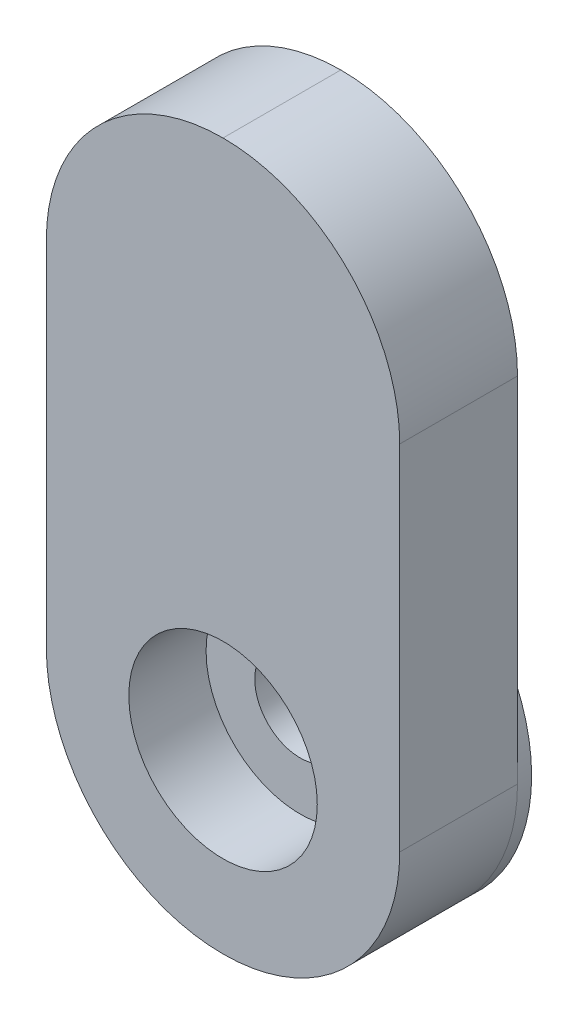
SolidWorks part; units mm, degrees
ref_plane "Front Plane" through (0, 0, 0) normal (0, 0, 1) x (1, 0, 0)
ref_plane "Top Plane" through (0, 0, 0) normal (0, 1, 0) x (1, 0, 0)
ref_plane "Right Plane" through (0, 0, 0) normal (1, 0, 0) x (0, 0, -1)
sketch "Sketch1" plane through (0, 0, 0) normal (0, 0, 1) x (1, 0, 0)
  line L1 (-9.525, 38.1) -> (9.525, 38.1)
  line L2 (-9.525, 38.1) -> (-9.525, 0)
  line L3 (-9.525, 0) -> (9.525, 0)
  line L4 (9.525, 38.1) -> (9.525, 0)
  line L5 (-9.525, 38.1) -> (9.525, 0) construction
  line L6 (-9.525, 0) -> (9.525, 38.1) construction
  point P0 (0, 19.05)
  dimension "D1" = 19.05
  dimension "D2" = 38.1
extrude "Boss-Extrude1" add sketch "Sketch1" along normal blind 6.35
hole_wizard "CBORE for #8 Socket Head Cap Screw1" positions "Sketch2" profile "Sketch3" counterbore size "#8" standard "ANSI Inch" end condition through all
sketch "Sketch2" plane through (0, 0, 6.35) normal (0, 0, 1) x (1, 0, 0)
  line L0 (-9.525, 0) -> (9.525, 0) construction
  point P0 (0, 9.525)
  dimension "D1" = 9.525
sketch "Sketch3" plane through (0, 9.525, 6.35) normal (1, 0, 0) x (0, -1, 0)
  line L0 (0, 0) -> (0, 6.35)
  line L1 (0, 6.35) -> (2.4575, 6.35)
  line L3 (2.4575, 6.35) -> (2.4575, 4.1656)
  line L4 (2.4575, 4.1656) -> (5.08, 4.1656)
  line L5 (5.08, 4.1656) -> (5.08, 0)
  line L7 (5.08, 0) -> (0, 0)
  line L11 (0, -6.35) -> (0, 107.95) construction
  dimension "Thru Hole Dia." = 4.9149
  dimension "Thru Hole Depth" = 6.35
  dimension "C'Bore Dia." = 10.16
  dimension "C'Bore Depth" = 4.1656
sketch "Sketch4" plane through (0, 0, 0) normal (0, 0, -1) x (-1, 0, 0)
  circle A0 centre (0, 9.525) radius 2.4575
  circle A1 centre (0, 9.525) radius 9.525
  circle A2 centre (0, 9.525) radius 2.4575 construction
  dimension "D1" = 19.05
extrude "Boss-Extrude2" add sketch "Sketch4" along normal blind 0.762
sketch "Sketch5" plane through (0, 0, -0.762) normal (0, 0, -1) x (-1, 0, 0)
  line L0 (-3.6422, 14.7266) -> (-1.4095, 11.538)
  line L1 (1.4095, 11.538) -> (3.6422, 14.7266)
  line L2 (0, 11.9825) -> (0, 15.875) construction
  line L3 (0, 9.525) -> (-1.4095, 11.538) construction
  line L4 (0, 9.525) -> (1.4095, 11.538) construction
  arc A0 (3.6422, 14.7266) -> (-3.6422, 14.7266) centre (0, 9.525) ccw
  arc A1 (1.4095, 11.538) -> (-1.4095, 11.538) centre (0, 9.525) ccw
  circle A2 centre (0, 9.525) radius 2.4575 construction
  point P3 (0, 0)
  dimension "D1" = 12.7
  dimension "D2" = 35
extrude "Boss-Extrude3" add sketch "Sketch5" along normal blind 2.54
fillet "Fillet1" radius 9.525 4 edges at (9.525, 38.1, 3.175) (-9.525, 38.1, 3.175) (9.525, 0, 3.175) (-9.525, 0, 3.175)
